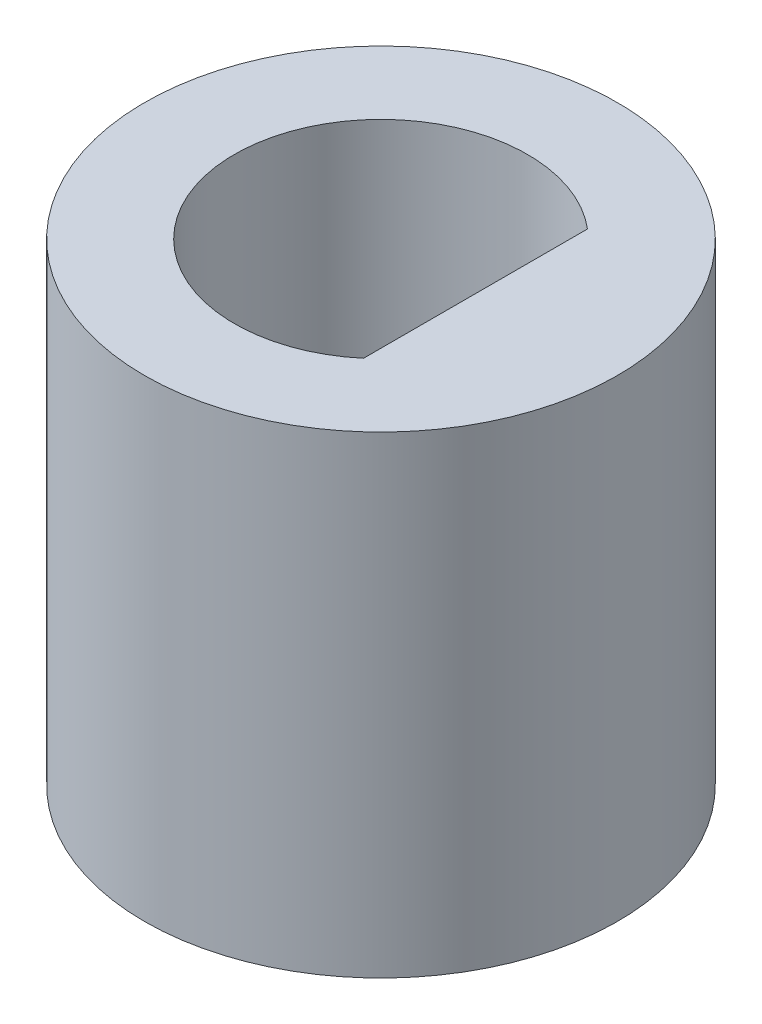
SolidWorks part; units mm, degrees
ref_plane "前视基准面" through (0, 0, 0) normal (0, 0, 1) x (1, 0, 0)
ref_plane "上视基准面" through (0, 0, 0) normal (0, 1, 0) x (1, 0, 0)
ref_plane "右视基准面" through (0, 0, 0) normal (1, 0, 0) x (0, 0, -1)
other "Configuration Table"
sketch "草图1" plane through (0, 0, 0) normal (0, 1, 0) x (1, 0, 0)
  line L0 (1, -1.1843) -> (1, 1.1843)
  circle A0 centre (0, 0) radius 2.5
  circle A1 centre (0, 0) radius 1.55
  circle A2 centre (0, 0) radius 1.4
  dimension "D1" = 3.1
  dimension "D2" = 5
  dimension "D4" = 2.8
  dimension "D3" = 1
extrude "凸台-拉伸1" add sketch "草图1" along normal blind 0.25 and the other way blind 0.25 contours A0 | A2
extrude "凸台-拉伸2" add sketch "草图1<3>" along normal blind 2.5 and the other way blind 2.5 contours A0 A1 | A2 L0 A1 | L0 A2 region at (1.0243, 0, 1.082) region at (1.1621, 0, 0) region at (-2.4293, 0, 0)
sketch "草图1<3>" plane through (0, 0, 0) normal (0, 1, 0) x (1, 0, 0) same geometry as "草图1"
